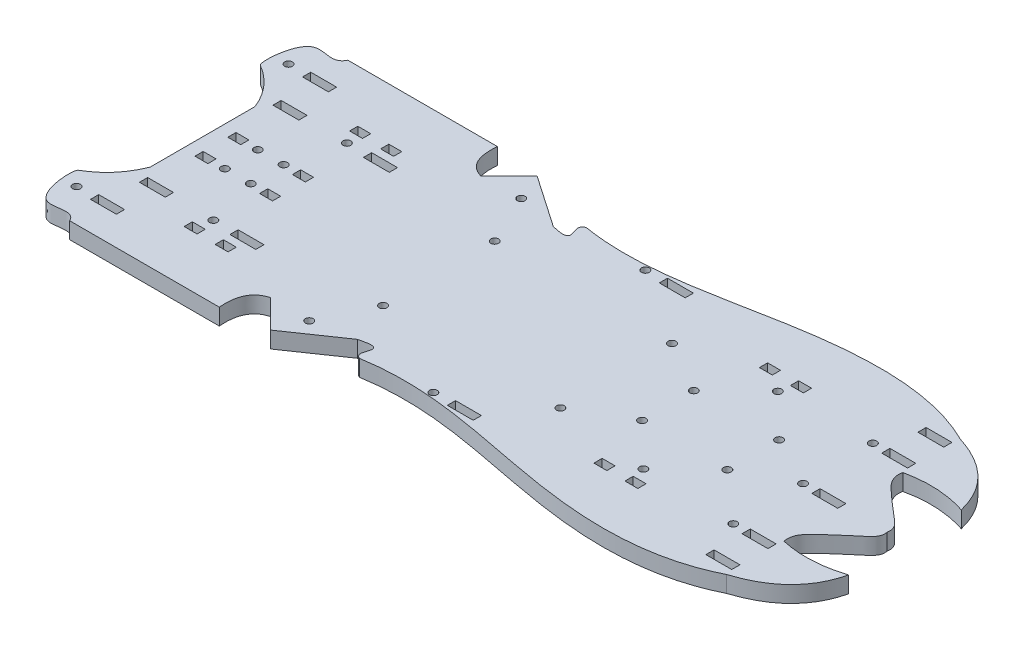
SolidWorks part; units mm, degrees
ref_plane "前视基准面" through (0, 0, 0) normal (0, 0, 1) x (1, 0, 0)
ref_plane "上视基准面" through (0, 0, 0) normal (0, 1, 0) x (1, 0, 0)
ref_plane "右视基准面" through (0, 0, 0) normal (1, 0, 0) x (0, 0, -1)
sketch "Sketch1" plane through (0, 0, 0) normal (0, 1, 0) x (1, 0, 0)
  line L0 (10.5269, -62.8027) -> (453.7588, -62.8027) construction
  line L1 (149.2972, 0) -> (-128.7028, 0) construction
  line L2 (-184.4845, 9.4891) -> (83.5155, 9.4891) construction
  dimension "D1" = 278
sketch "Sketch2" plane through (0, 0, 0) normal (0, 1, 0) x (1, 0, 0)
  line L0 (-170.8604, 0) -> (166.3868, 0) construction
  line L1 (-63.8404, 53.7851) -> (-121.7032, 53.7851)
  line L2 (-124.1047, 20.2534) -> (-124.1047, -20.2534)
  line L3 (-63.8404, -53.7851) -> (-121.7032, -53.7851)
  spline S0 degree 3 poles (140.662, 0) (141.3872, 2.7611) (135.7365, 7.3542) (128.6934, 13.5063) (122.9355, 18.9325) (123.7573, 22.9914) knots 0 0 0 0 0.249977 0.654822 1 1 1 1
  spline S1 degree 2 poles (123.7573, 22.9914) (135.6661, 25.6419) (147.5593, 21.7995) knots 0 0 0 1 1 1
  spline S2 degree 2 poles (147.5593, 21.7995) (143.4728, 38.9852) (123.7573, 45.2702) knots 0 0 0 1 1 1
  spline S3 degree 3 poles (123.7573, 45.2702) (104.0876, 55.1301) (53.5469, 54.4384) (7.187, 39.3743) (-19.5545, 43.8388) knots 0 0 0 0 0.449955 1 1 1 1
  spline S4 degree 3 poles (-19.5545, 43.8388) (-24.3449, 42.1677) (-14.2503, 34.7826) (-26.262, 37.8236) knots 0 0 0 0 1 1 1 1
  spline S5 degree 1 poles (-26.262, 37.8236) (-46.3096, 51.5978) knots 0 0 1 1
  spline S6 degree 1 poles (-46.3096, 51.5978) (-57.1158, 40.6993) knots 0 0 1 1
  spline S7 degree 2 poles (-57.1158, 40.6993) (-64.808, 42.8132) (-63.8404, 53.7851) knots 0 0 0 1 1 1
  spline S8 degree 3 poles (-121.7032, 53.7851) (-123.8199, 49.2101) (-137.2417, 58.4235) (-138.2637, 36.4234) (-136.9986, 35.2212) knots 0 0 0 0 0.398286 1 1 1 1
  spline S9 degree 2 poles (-136.9986, 35.2212) (-127.8855, 29.9113) (-124.1047, 20.2534) knots 0 0 0 1 1 1
  spline S10 degree 2 poles (-136.9986, -35.2212) (-127.8855, -29.9113) (-124.1047, -20.2534) knots 0 0 0 1 1 1
  spline S11 degree 3 poles (-121.7032, -53.7851) (-123.8199, -49.2101) (-137.2417, -58.4235) (-138.2637, -36.4234) (-136.9986, -35.2212) knots 0 0 0 0 0.398286 1 1 1 1
  spline S12 degree 2 poles (-57.1158, -40.6993) (-64.808, -42.8132) (-63.8404, -53.7851) knots 0 0 0 1 1 1
  spline S13 degree 1 poles (-46.3096, -51.5978) (-57.1158, -40.6993) knots 0 0 1 1
  spline S14 degree 1 poles (-26.262, -37.8236) (-46.3096, -51.5978) knots 0 0 1 1
  spline S15 degree 3 poles (-19.5545, -43.8388) (-24.3449, -42.1677) (-14.2503, -34.7826) (-26.262, -37.8236) knots 0 0 0 0 1 1 1 1
  spline S16 degree 3 poles (123.7573, -45.2702) (104.0876, -55.1301) (53.5469, -54.4384) (7.187, -39.3743) (-19.5545, -43.8388) knots 0 0 0 0 0.449955 1 1 1 1
  spline S17 degree 2 poles (147.5593, -21.7995) (143.4728, -38.9852) (123.7573, -45.2702) knots 0 0 0 1 1 1
  spline S18 degree 2 poles (123.7573, -22.9914) (135.6661, -25.6419) (147.5593, -21.7995) knots 0 0 0 1 1 1
  spline S19 degree 3 poles (140.662, 0) (141.3872, -2.7611) (135.7365, -7.3542) (128.6934, -13.5063) (122.9355, -18.9325) (123.7573, -22.9914) knots 0 0 0 0 0.249977 0.654822 1 1 1 1
  point P59 (-124.1047, 0)
extrude "Boss-Extrude1" add sketch "Sketch2" along normal blind 6.35
sketch "Sketch3" plane through (0, 6.35, 0) normal (0, 1, 0) x (1, 0, 0)
  line L0 (-136.5043, 0) -> (151.5478, 0) construction
  line L1 (172.4729, 41) -> (-148.1908, 41) construction
  line L2 (68.1603, 64.0219) -> (68.1603, 18.9749) construction
  line L3 (123.1603, 42.5875) -> (113.1603, 42.5875)
  line L4 (123.1603, 42.5875) -> (123.1603, 39.4125)
  line L5 (123.1603, 39.4125) -> (113.1603, 39.4125)
  line L6 (113.1603, 42.5875) -> (113.1603, 39.4125)
  line L7 (123.1603, 42.5875) -> (113.1603, 39.4125) construction
  line L8 (123.1603, 39.4125) -> (113.1603, 42.5875) construction
  line L9 (13.1603, 39.4125) -> (23.1603, 42.5875) construction
  line L10 (13.1603, 42.5875) -> (23.1603, 39.4125) construction
  line L11 (23.1603, 42.5875) -> (23.1603, 39.4125)
  line L12 (13.1603, 39.4125) -> (23.1603, 39.4125)
  line L13 (13.1603, 42.5875) -> (13.1603, 39.4125)
  line L14 (13.1603, 42.5875) -> (23.1603, 42.5875)
  line L15 (-0.8397, 68.81) -> (-0.8397, 15.386) construction
  line L16 (-124.8397, 39.4125) -> (-114.8397, 42.5875) construction
  line L17 (-124.8397, 42.5875) -> (-114.8397, 39.4125) construction
  line L18 (-114.8397, 42.5875) -> (-114.8397, 39.4125)
  line L19 (-124.8397, 39.4125) -> (-114.8397, 39.4125)
  line L20 (-124.8397, 42.5875) -> (-124.8397, 39.4125)
  line L21 (-124.8397, 42.5875) -> (-114.8397, 42.5875)
  line L22 (-124.8397, -42.5875) -> (-114.8397, -39.4125) construction
  line L23 (-124.8397, -39.4125) -> (-114.8397, -42.5875) construction
  line L24 (13.1603, -42.5875) -> (23.1603, -39.4125) construction
  line L25 (13.1603, -39.4125) -> (23.1603, -42.5875) construction
  line L26 (123.1603, -39.4125) -> (113.1603, -42.5875) construction
  line L27 (123.1603, -42.5875) -> (113.1603, -39.4125) construction
  line L28 (-124.8397, -42.5875) -> (-114.8397, -42.5875)
  line L29 (-124.8397, -42.5875) -> (-124.8397, -39.4125)
  line L30 (-124.8397, -39.4125) -> (-114.8397, -39.4125)
  line L31 (-114.8397, -42.5875) -> (-114.8397, -39.4125)
  line L32 (13.1603, -42.5875) -> (23.1603, -42.5875)
  line L33 (13.1603, -42.5875) -> (13.1603, -39.4125)
  line L34 (13.1603, -39.4125) -> (23.1603, -39.4125)
  line L35 (23.1603, -42.5875) -> (23.1603, -39.4125)
  line L36 (113.1603, -42.5875) -> (113.1603, -39.4125)
  line L37 (123.1603, -39.4125) -> (113.1603, -39.4125)
  line L38 (123.1603, -42.5875) -> (123.1603, -39.4125)
  line L39 (123.1603, -42.5875) -> (113.1603, -42.5875)
  line L40 (118.1603, 59.1499) -> (118.1603, -18.3287) construction
  line L41 (123.1603, 1.5875) -> (113.1603, 1.5875)
  line L42 (123.1603, -1.5875) -> (113.1603, -1.5875)
  line L43 (123.1603, -1.5875) -> (113.1603, 1.5875) construction
  line L44 (123.1603, 1.5875) -> (123.1603, -1.5875)
  line L45 (123.1603, 1.5875) -> (113.1603, -1.5875) construction
  line L46 (113.1603, 1.5875) -> (113.1603, -1.5875)
  line L47 (123.1603, 28.5875) -> (113.1603, 28.5875)
  line L48 (123.1603, 25.4125) -> (113.1603, 25.4125)
  line L49 (123.1603, 28.5875) -> (123.1603, 25.4125)
  line L50 (113.1603, 28.5875) -> (113.1603, 25.4125)
  line L51 (123.1603, 25.4125) -> (113.1603, 28.5875) construction
  line L52 (123.1603, 28.5875) -> (113.1603, 25.4125) construction
  line L53 (123.1603, -25.4125) -> (113.1603, -25.4125)
  line L54 (123.1603, -28.5875) -> (113.1603, -25.4125) construction
  line L55 (123.1603, -28.5875) -> (123.1603, -25.4125)
  line L56 (123.1603, -25.4125) -> (113.1603, -28.5875) construction
  line L57 (113.1603, -28.5875) -> (113.1603, -25.4125)
  line L58 (123.1603, -28.5875) -> (113.1603, -28.5875)
  line L59 (118.1603, 27) -> (100.6919, 27) construction
  line L60 (118.1603, -27) -> (81.8349, -27) construction
  circle A0 centre (6.1603, 41) radius 1.5
  circle A1 centre (-41.8397, 41) radius 1.5
  circle A2 centre (-131.8397, 41) radius 1.5
  circle A3 centre (6.1603, -41) radius 1.5
  circle A4 centre (-41.8397, -41) radius 1.5
  circle A5 centre (-131.8397, -41) radius 1.5
  circle A6 centre (108.1603, 27) radius 1.5
  circle A7 centre (108.1603, 0) radius 1.5
  circle A8 centre (108.1603, -27) radius 1.5
  point P5 (118.1603, 41)
  point P10 (133.1603, 41)
  point P17 (18.1603, 41)
  point P24 (-119.8397, 41)
  point P37 (-119.8397, -41)
  point P38 (18.1603, -41)
  point P39 (118.1603, -41)
  point P54 (118.1603, 0)
  point P60 (118.1603, 27)
  dimension "D8" = 3
  dimension "D9" = 3
  dimension "D11" = 3
  dimension "D18" = 3
  dimension "D19" = 3
  dimension "D22" = 3
  dimension "D1" = 41
  dimension "D2" = 10
  dimension "D3" = 3.175
  dimension "D4" = 15
  dimension "D5" = 100
  dimension "D6" = 238
  dimension "D7" = 117
  dimension "D10" = 165
  dimension "D12" = 255
  dimension "D13" = 10
  dimension "D14" = 3.175
  dimension "D16" = 27
  dimension "D17" = 15
  dimension "D20" = 15
  dimension "D21" = 15
  dimension "D15" = 2
extrude "Cut-Extrude1" cut sketch "Sketch3" against normal through all
sketch "Sketch5" plane through (0, 6.35, 0) normal (0, 1, 0) x (1, 0, 0)
  line L0 (-137.8228, 0) -> (156.6911, 0) construction
  line L1 (69.3603, 63.44) -> (69.3603, -23.9466) construction
  line L3 (-89.1347, 32) -> (69.3603, 32) construction
  line L5 (72.8603, 33.5875) -> (77.8603, 30.4125) construction
  line L6 (65.8603, 30.4125) -> (60.8603, 30.4125)
  line L7 (65.8603, 30.4125) -> (65.8603, 33.5875)
  line L8 (65.8603, 33.5875) -> (60.8603, 33.5875)
  line L9 (60.8603, 30.4125) -> (60.8603, 33.5875)
  line L10 (65.8603, 30.4125) -> (60.8603, 33.5875) construction
  line L11 (65.8603, 33.5875) -> (60.8603, 30.4125) construction
  line L12 (72.8603, 30.4125) -> (77.8603, 33.5875) construction
  line L13 (77.8603, 30.4125) -> (77.8603, 33.5875)
  line L14 (72.8603, 33.5875) -> (77.8603, 33.5875)
  line L15 (72.8603, 30.4125) -> (72.8603, 33.5875)
  line L16 (72.8603, 30.4125) -> (77.8603, 30.4125)
  line L17 (-89.1347, 47.3689) -> (-89.1347, -19.032) construction
  line L18 (-124.1047, 20.2534) -> (-124.1047, -20.2534) construction
  line L19 (-9.8872, 32) -> (-9.8872, 71.4552) construction
  line L20 (-92.6347, 30.4125) -> (-97.6347, 33.5875) construction
  line L21 (-85.6347, 33.5875) -> (-80.6347, 30.4125) construction
  line L22 (-85.6347, 30.4125) -> (-80.6347, 33.5875) construction
  line L23 (-92.6347, 33.5875) -> (-97.6347, 30.4125) construction
  line L24 (-92.6347, 30.4125) -> (-97.6347, 30.4125)
  line L25 (-92.6347, 30.4125) -> (-92.6347, 33.5875)
  line L26 (-92.6347, 33.5875) -> (-97.6347, 33.5875)
  line L27 (-97.6347, 30.4125) -> (-97.6347, 33.5875)
  line L28 (-80.6347, 30.4125) -> (-80.6347, 33.5875)
  line L29 (-85.6347, 33.5875) -> (-80.6347, 33.5875)
  line L30 (-85.6347, 30.4125) -> (-85.6347, 33.5875)
  line L31 (-85.6347, 30.4125) -> (-80.6347, 30.4125)
  line L32 (72.8603, -30.4125) -> (77.8603, -33.5875) construction
  line L33 (65.8603, -33.5875) -> (60.8603, -30.4125) construction
  line L34 (65.8603, -30.4125) -> (60.8603, -33.5875) construction
  line L35 (72.8603, -33.5875) -> (77.8603, -30.4125) construction
  line L36 (72.8603, -30.4125) -> (77.8603, -30.4125)
  line L37 (72.8603, -30.4125) -> (72.8603, -33.5875)
  line L38 (72.8603, -33.5875) -> (77.8603, -33.5875)
  line L39 (77.8603, -30.4125) -> (77.8603, -33.5875)
  line L40 (60.8603, -30.4125) -> (60.8603, -33.5875)
  line L41 (65.8603, -33.5875) -> (60.8603, -33.5875)
  line L42 (65.8603, -30.4125) -> (65.8603, -33.5875)
  line L43 (65.8603, -30.4125) -> (60.8603, -30.4125)
  line L44 (-92.6347, -33.5875) -> (-97.6347, -30.4125) construction
  line L45 (-85.6347, -30.4125) -> (-80.6347, -33.5875) construction
  line L46 (-85.6347, -33.5875) -> (-80.6347, -30.4125) construction
  line L47 (-92.6347, -30.4125) -> (-97.6347, -33.5875) construction
  line L48 (-85.6347, -30.4125) -> (-80.6347, -30.4125)
  line L49 (-85.6347, -30.4125) -> (-85.6347, -33.5875)
  line L50 (-85.6347, -33.5875) -> (-80.6347, -33.5875)
  line L51 (-80.6347, -30.4125) -> (-80.6347, -33.5875)
  line L52 (-97.6347, -30.4125) -> (-97.6347, -33.5875)
  line L53 (-92.6347, -33.5875) -> (-97.6347, -33.5875)
  line L54 (-92.6347, -30.4125) -> (-92.6347, -33.5875)
  line L55 (-92.6347, -30.4125) -> (-97.6347, -30.4125)
  point P11 (63.3603, 32)
  point P20 (75.3603, 32)
  point P31 (-95.1347, 32)
  point P32 (-83.1347, 32)
  point P41 (75.3603, -32)
  point P42 (63.3603, -32)
  point P51 (-83.1347, -32)
  point P52 (-95.1347, -32)
  dimension "D1" = 193.465
  dimension "D2" = 32
  dimension "D3" = 3.175
  dimension "D4" = 5
  dimension "D5" = 12
  dimension "D6" = 34.97
extrude "Cut-Extrude2" cut sketch "Sketch5" against normal through all
sketch "Sketch6" plane through (0, 6.35, 0) normal (0, 1, 0) x (1, 0, 0)
  line L0 (0, 0) -> (-67.1181, 0) construction
  line L1 (55.8953, 18.4804) -> (55.8953, -19.3911) construction
  line L2 (-124.1047, 20.2534) -> (-124.1047, -20.2534) construction
  line L3 (72.3953, 10) -> (72.3953, 23.5486) construction
  line L4 (55.8953, 10) -> (88.8953, 10) construction
  line L5 (1.6053, 18.4804) -> (1.6053, -20.559) construction
  circle A0 centre (55.8953, 10) radius 1.5
  circle A1 centre (88.8953, 10) radius 1.5
  circle A2 centre (72.3953, 26) radius 1.5
  circle A3 centre (88.8953, -10) radius 1.5
  circle A4 centre (55.8953, -10) radius 1.5
  circle A5 centre (72.3953, -26) radius 1.5
  circle A6 centre (35.8953, 21.59) radius 1.5
  circle A7 centre (35.8953, -21.59) radius 1.5
  circle A8 centre (-32.6847, -21.59) radius 1.5
  circle A9 centre (-32.6847, 21.59) radius 1.5
  dimension "D1" = 3
  dimension "D3" = 3
  dimension "D5" = 3
  dimension "D8" = 3
  dimension "D2" = 180
  dimension "D4" = 33
  dimension "D6" = 20
  dimension "D7" = 52
  dimension "D9" = 68.58
  dimension "D10" = 43.18
  dimension "D11" = 20
extrude "Cut-Extrude3" cut sketch "Sketch6" against normal through all
sketch "Sketch7" plane through (0, 6.35, 0) normal (0, 1, 0) x (1, 0, 0)
  line L0 (0, 0) -> (-134.4635, 0) construction
  line L1 (-116.1047, 29.0267) -> (-116.1047, -8.1812) construction
  line L2 (-124.1047, 20.2534) -> (-124.1047, -20.2534) construction
  line L3 (-111.1047, 24.2375) -> (-121.1047, 24.2375)
  line L4 (-111.1047, 24.2375) -> (-111.1047, 27.4125)
  line L5 (-111.1047, 27.4125) -> (-121.1047, 27.4125)
  line L6 (-121.1047, 24.2375) -> (-121.1047, 27.4125)
  line L7 (-111.1047, 24.2375) -> (-121.1047, 27.4125) construction
  line L8 (-111.1047, 27.4125) -> (-121.1047, 24.2375) construction
  line L9 (-97.6347, 30.4125) -> (-92.6347, 30.4125) construction
  line L10 (-98.6047, 25.825) -> (-98.6047, 10.3174) construction
  line L11 (-86.1047, 27.4125) -> (-76.1047, 24.2375) construction
  line L12 (-86.1047, 24.2375) -> (-76.1047, 27.4125) construction
  line L13 (-76.1047, 24.2375) -> (-76.1047, 27.4125)
  line L14 (-86.1047, 27.4125) -> (-76.1047, 27.4125)
  line L15 (-86.1047, 24.2375) -> (-86.1047, 27.4125)
  line L16 (-86.1047, 24.2375) -> (-76.1047, 24.2375)
  line L17 (-86.1047, -24.2375) -> (-76.1047, -27.4125) construction
  line L18 (-86.1047, -27.4125) -> (-76.1047, -24.2375) construction
  line L19 (-86.1047, -24.2375) -> (-76.1047, -24.2375)
  line L20 (-86.1047, -24.2375) -> (-86.1047, -27.4125)
  line L21 (-86.1047, -27.4125) -> (-76.1047, -27.4125)
  line L22 (-76.1047, -24.2375) -> (-76.1047, -27.4125)
  line L23 (-111.1047, -27.4125) -> (-121.1047, -24.2375) construction
  line L24 (-111.1047, -24.2375) -> (-121.1047, -27.4125) construction
  line L25 (-121.1047, -24.2375) -> (-121.1047, -27.4125)
  line L26 (-111.1047, -27.4125) -> (-121.1047, -27.4125)
  line L27 (-111.1047, -24.2375) -> (-111.1047, -27.4125)
  line L28 (-111.1047, -24.2375) -> (-121.1047, -24.2375)
  line L29 (-116.1047, 25.825) -> (-89.6698, 25.825) construction
  circle A0 centre (-94.1047, 25.825) radius 1.5
  circle A1 centre (-94.1047, -25.825) radius 1.5
  point P5 (-116.1047, 25.825)
  point P20 (-81.1047, 25.825)
  point P25 (-81.1047, -25.825)
  point P30 (-116.1047, -25.825)
  dimension "D6" = 3
  dimension "D1" = 3.175
  dimension "D2" = 10
  dimension "D3" = 8
  dimension "D4" = 3
  dimension "D5" = 25
  dimension "D7" = 8
extrude "Cut-Extrude4" cut sketch "Sketch7" against normal through all
sketch "Sketch8" plane through (0, 6.35, 0) normal (0, 1, 0) x (1, 0, 0)
  line L0 (0, 0) -> (-153.5755, 0) construction
  line L1 (-104.1047, 19.1747) -> (-104.1047, -20.3107) construction
  line L2 (-138.7268, 6.35) -> (-93.9689, 6.35) construction
  line L5 (-89.1047, 7.9375) -> (-94.1047, 4.7625) construction
  line L6 (-119.1047, 4.7625) -> (-114.1047, 4.7625)
  line L7 (-119.1047, 4.7625) -> (-119.1047, 7.9375)
  line L8 (-119.1047, 7.9375) -> (-114.1047, 7.9375)
  line L9 (-114.1047, 4.7625) -> (-114.1047, 7.9375)
  line L10 (-119.1047, 4.7625) -> (-114.1047, 7.9375) construction
  line L11 (-119.1047, 7.9375) -> (-114.1047, 4.7625) construction
  line L12 (-89.1047, 4.7625) -> (-94.1047, 7.9375) construction
  line L13 (-94.1047, 4.7625) -> (-94.1047, 7.9375)
  line L14 (-89.1047, 7.9375) -> (-94.1047, 7.9375)
  line L15 (-89.1047, 4.7625) -> (-89.1047, 7.9375)
  line L16 (-89.1047, 4.7625) -> (-94.1047, 4.7625)
  line L17 (-124.1047, 20.2534) -> (-124.1047, -20.2534) construction
  line L18 (-89.1047, -4.7625) -> (-94.1047, -7.9375) construction
  line L19 (-119.1047, -7.9375) -> (-114.1047, -4.7625) construction
  line L20 (-119.1047, -4.7625) -> (-114.1047, -7.9375) construction
  line L21 (-89.1047, -7.9375) -> (-94.1047, -4.7625) construction
  line L22 (-89.1047, -4.7625) -> (-94.1047, -4.7625)
  line L23 (-89.1047, -4.7625) -> (-89.1047, -7.9375)
  line L24 (-89.1047, -7.9375) -> (-94.1047, -7.9375)
  line L25 (-94.1047, -4.7625) -> (-94.1047, -7.9375)
  line L26 (-114.1047, -4.7625) -> (-114.1047, -7.9375)
  line L27 (-119.1047, -7.9375) -> (-114.1047, -7.9375)
  line L28 (-119.1047, -4.7625) -> (-119.1047, -7.9375)
  line L29 (-119.1047, -4.7625) -> (-114.1047, -4.7625)
  circle A0 centre (-109.1047, 6.35) radius 1.5
  circle A1 centre (-99.1047, 6.35) radius 1.5
  circle A2 centre (-99.1047, -6.35) radius 1.5
  circle A3 centre (-109.1047, -6.35) radius 1.5
  point P9 (-116.6047, 6.35)
  point P18 (-91.6047, 6.35)
  point P37 (-91.6047, -6.35)
  point P38 (-116.6047, -6.35)
  dimension "D6" = 3
  dimension "D1" = 12.7
  dimension "D2" = 3.175
  dimension "D3" = 5
  dimension "D4" = 25
  dimension "D5" = 5
  dimension "D7" = 10
extrude "Cut-Extrude5" cut sketch "Sketch8" against normal through all
